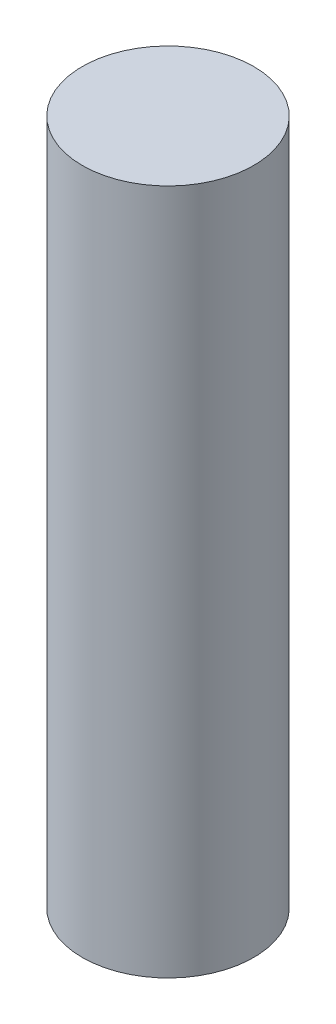
SolidWorks part; units mm, degrees
ref_plane "Front Plane" through (0, 0, 0) normal (0, 0, 1) x (1, 0, 0)
ref_plane "Top Plane" through (0, 0, 0) normal (0, 1, 0) x (1, 0, 0)
ref_plane "Right Plane" through (0, 0, 0) normal (1, 0, 0) x (0, 0, -1)
sketch "Sketch1" plane through (0, 0, 0) normal (0, 1, 0) x (1, 0, 0)
  circle A0 centre (0, 0) radius 0.75
extrude "Boss-Extrude1" add sketch "Sketch1" along normal blind 6
ref_plane "Plane1" through (0, 3, 0) normal (0, 1, 0) x (1, 0, 0)
ref_axis "Axis1" through (0, 6, 0) along (0, -1, 0)
ref_plane "Plane2" through (0, 3, 0) normal (0, 1, 0) x (1, 0, 0)
ref_point "Point1"
